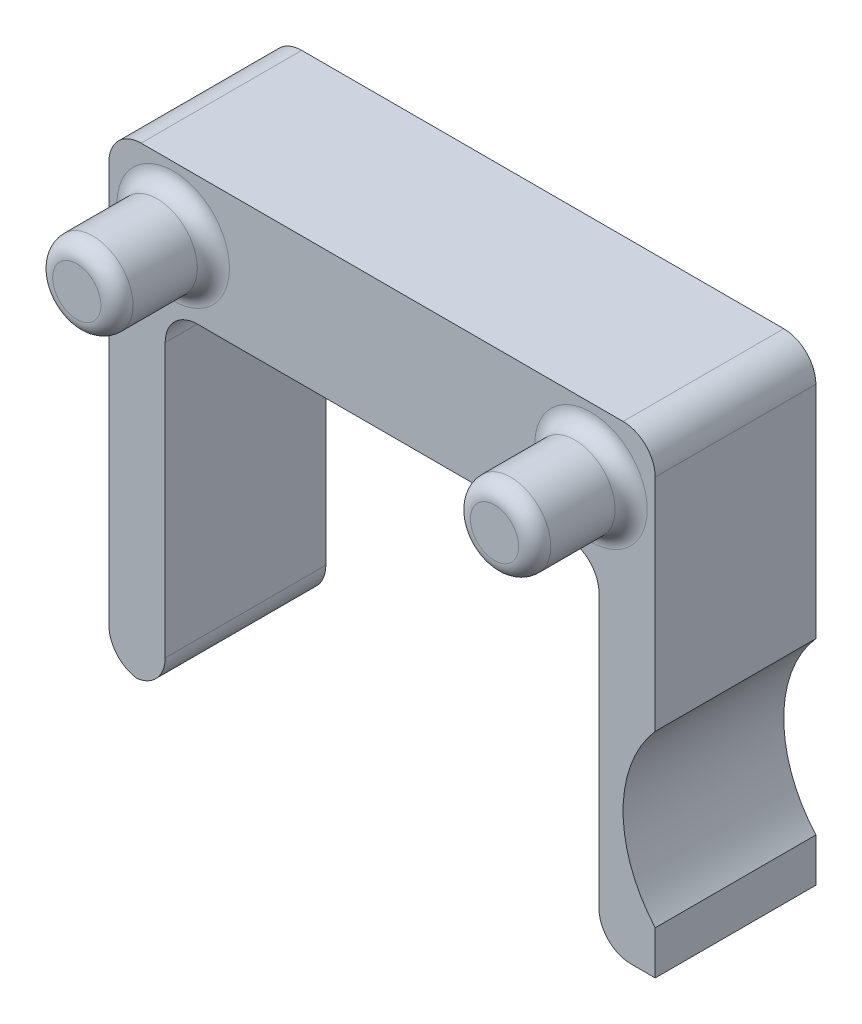
SolidWorks part; units mm, degrees
ref_plane "Front Plane" through (0, 0, 0) normal (0, 0, 1) x (1, 0, 0)
ref_plane "Top Plane" through (0, 0, 0) normal (0, 1, 0) x (1, 0, 0)
ref_plane "Right Plane" through (0, 0, 0) normal (1, 0, 0) x (0, 0, -1)
sketch "Sketch1" plane through (0, 0, 0) normal (0, 0, 1) x (1, 0, 0)
  line L0 (-7.8963, 3.6156) -> (5.1037, 3.6156) construction
  line L1 (-8.1463, 1.6156) -> (-8.1463, -8.8844)
  line L2 (-8.1463, -8.8844) -> (-9.8963, -8.8844)
  line L3 (-9.8963, -8.8844) -> (-9.8963, 5.6156)
  line L4 (-9.8963, 5.6156) -> (7.1037, 5.6156)
  line L5 (7.1037, 5.6156) -> (7.1037, -2.2387)
  line L6 (7.1037, -8.8844) -> (5.3537, -8.8844)
  line L7 (5.3537, -8.8844) -> (5.3537, 1.6156)
  line L8 (5.3537, 1.6156) -> (-8.1463, 1.6156)
  line L9 (7.1037, -7.5302) -> (7.1037, -8.8844)
  circle A0 centre (-7.8963, 3.6156) radius 1.25
  circle A1 centre (5.1037, 3.6156) radius 1.25
  arc A2 (7.1037, -2.2387) -> (7.1037, -7.5302) centre (10.1037, -4.8844) ccw
  dimension "D1" = 13
  dimension "D2" = 2.5
  dimension "D3" = 2.5
  dimension "D9" = 8
  dimension "D4" = 12.5
  dimension "D5" = 2
  dimension "D6" = 1.75
  dimension "D7" = 1.75
  dimension "D8" = 4
  dimension "D10" = 4.75
  dimension "D11" = 12.5
  dimension "D12" = 2
extrude "Boss-Extrude1" add sketch "Sketch1" along normal blind 5
sketch "Sketch2" plane through (0, 0, 5) normal (0, 0, 1) x (1, 0, 0)
  circle A0 centre (-7.8963, 3.6156) radius 1.25
  circle A1 centre (5.1037, 3.6156) radius 1.25
  circle A2 centre (-7.8963, 3.6156) radius 1.25 construction
  circle A3 centre (5.1037, 3.6156) radius 1.25 construction
extrude "Boss-Extrude2" add sketch "Sketch2" along normal blind 3 and the other way blind 5
fillet "Fillet1" radius 1 7 edges at (-9.8963, 5.6156, 2.5) (7.1037, 5.6156, 2.5) (-8.1463, 1.6156, 2.5) (5.3537, 1.6156, 2.5) (5.3537, -8.8844, 2.5) (-8.1463, -8.8844, 2.5) (-9.8963, -8.8844, 2.5)
fillet "Fillet2" radius 0.5 4 edges at (6.3537, 3.6156, 8) (-6.6463, 3.6156, 8) (6.3537, 3.6156, 5) (-6.6463, 3.6156, 5)
